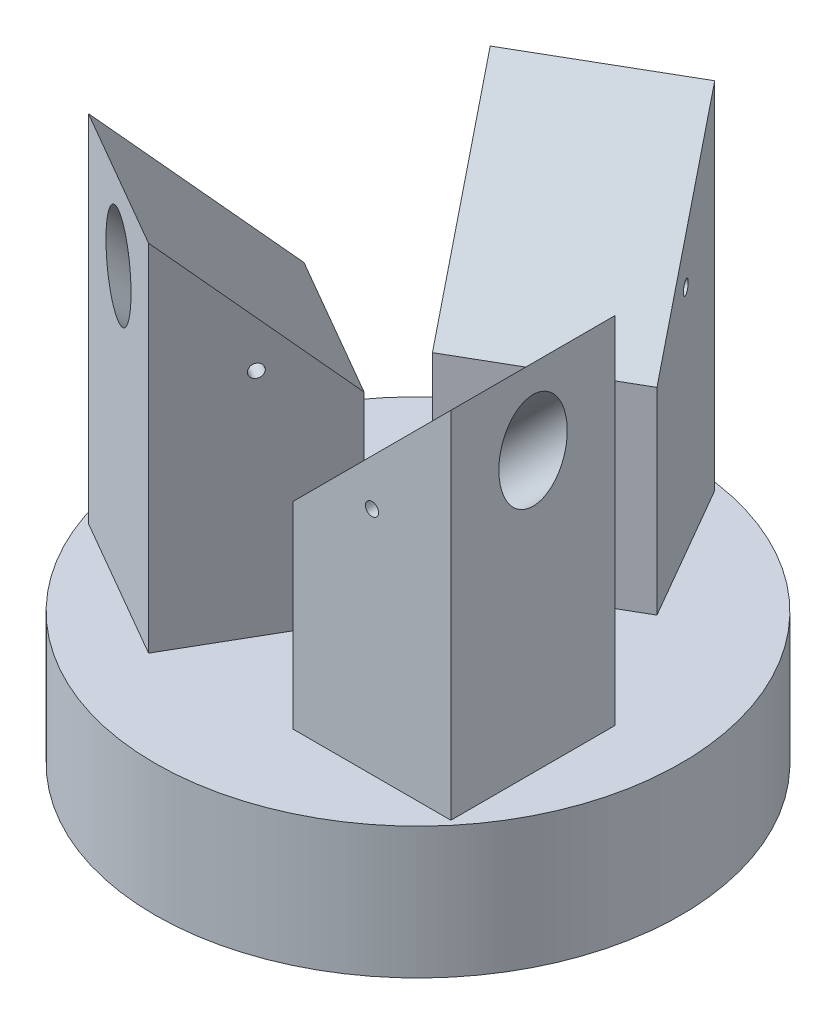
SolidWorks part; units mm, degrees
ref_plane "Front Plane" through (0, 0, 0) normal (0, 0, 1) x (1, 0, 0)
ref_plane "Top Plane" through (0, 0, 0) normal (0, 1, 0) x (1, 0, 0)
ref_plane "Right Plane" through (0, 0, 0) normal (1, 0, 0) x (0, 0, -1)
sketch "Sketch1" plane through (0, 0, 0) normal (0, 1, 0) x (1, 0, 0)
  circle A0 centre (0, 0) radius 50.8
  dimension "D1" = 101.6
extrude "Boss-Extrude1" add sketch "Sketch1" along normal blind 25.4
sketch "Sketch2" plane through (0, 0, 0) normal (0, -1, 0) x (1, 0, 0)
  line L0 (0, 0) -> (-25.4, 0) construction
  line L1 (0, 0) -> (0, 50.8) construction
  circle A0 centre (-25.4, 0) radius 1.27
  circle A1 centre (0, 0) radius 50.8 construction
  circle A2 centre (0, 25.4) radius 1.27
  circle A3 centre (25.4, 0) radius 1.27
  circle A4 centre (0, -25.4) radius 1.27
  point P3 (0, 0)
  point P9 (0, -25.4)
  point P17 (0, 0)
  dimension "D1" = 90
  dimension "D4" = 25.4
  dimension "D5" = 25.4
  dimension "D6" = 2.54
  dimension "D2" = 25.4
  dimension "D3" = 4
extrude "Cut-Extrude1" cut sketch "Sketch2" against normal blind 12.7
ref_axis "Axis1" through (0, 25.4, 0) along (0, -1, 0)
sketch "Sketch3" plane through (0, 25.4, 0) normal (0, 1, 0) x (1, 0, 0)
  line L0 (0, 0) -> (50.8, 0)
  circle A0 centre (0, 0) radius 50.8 construction
ref_plane "Plane1" through (0, 0, 0) normal (0, 0, 1) x (1, 0, 0)
sketch "Sketch4" plane through (0, 0, 0) normal (0, 0, 1) x (1, 0, 0)
  line L0 (7.62, 25.4) -> (7.62, 63.5)
  line L1 (38.1, 25.4) -> (7.62, 25.4)
  line L2 (38.1, 25.4) -> (38.1, 93.98)
  line L3 (38.1, 93.98) -> (7.62, 63.5)
  line L4 (7.62, 63.5) -> (52.1327, 63.5) construction
  dimension "D1" = 45
extrude "Boss-Extrude2" add sketch "Sketch4" along normal blind 31.75
sketch "Sketch5" plane through (38.1, 0, 0) normal (1, 0, 0) x (0, 0, -1)
  line L0 (-15.875, 93.98) -> (-15.875, 81.28) construction
  line L1 (-31.75, 93.98) -> (0, 93.98) construction
  line L2 (-15.875, 95.504) -> (-2.6499, 95.504)
  circle A0 centre (-15.875, 81.28) radius 14.224
  dimension "D1" = 12.7
ref_plane "Plane2" through (66.802, 66.802, 0) normal (0.7071, 0.7071, 0) x (0, 0, -1)
sketch "Sketch7" plane through (7.62, 0, 0) normal (-1, 0, 0) x (0, 0, 1)
  line L0 (15.875, 63.5) -> (15.875, 50.8) construction
  line L1 (31.75, 63.5) -> (0, 63.5) construction
  line L3 (15.875, 57.404) -> (28.7041, 57.404)
  circle A0 centre (15.875, 50.8) radius 6.604
  dimension "D1" = 12.7
ref_plane "Plane3" through (32.512, 32.512, 0) normal (-0.7071, -0.7071, 0) x (0, 0, 1)
sketch "Sketch9" plane through (66.802, 66.802, 0) normal (0.7071, 0.7071, 0) x (0, 0, -1)
  line L0 (-15.875, 40.5908) -> (-15.875, 29.1608) construction
  circle A0 centre (-15.875, 29.1608) radius 6.604
  dimension "D1" = 11.43
extrude "Cut-Extrude2" cut sketch "Sketch9" against normal blind 68.58
sketch "Sketch10" plane through (0, 0, 31.75) normal (0, 0, 1) x (1, 0, 0)
  line L0 (22.86, 78.74) -> (22.86, 69.85) construction
  line L1 (38.1, 93.98) -> (7.62, 63.5) construction
  circle A0 centre (22.86, 69.85) radius 1.27
extrude "Cut-Extrude3" cut sketch "Sketch10" against normal blind 68.58
pattern_circular "CirPattern3" count 3 over 360 about axis through (0, 25.4, 0) along (0, -1, 0) of "Boss-Extrude2", "Cut-Extrude3", "Cut-Extrude2"
